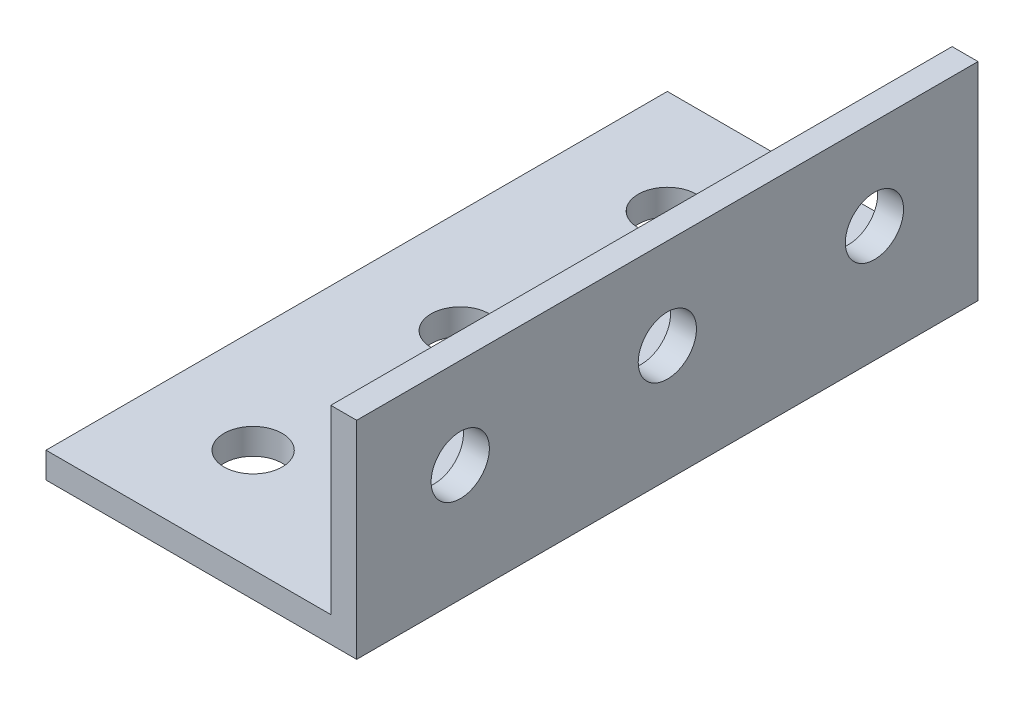
SolidWorks part; units mm, degrees
ref_plane "Front Plane" through (0, 0, 0) normal (0, 0, 1) x (1, 0, 0)
ref_plane "Top Plane" through (0, 0, 0) normal (0, 1, 0) x (1, 0, 0)
ref_plane "Right Plane" through (0, 0, 0) normal (1, 0, 0) x (0, 0, -1)
sketch "Sketch1" plane through (0, 0, 0) normal (0, 0, 1) x (1, 0, 0)
  line L0 (0, 0) -> (38.1, 0)
  line L1 (38.1, 0) -> (38.1, 25.4)
  line L2 (38.1, 25.4) -> (34.925, 25.4)
  line L3 (34.925, 25.4) -> (34.925, 3.175)
  line L4 (34.925, 3.175) -> (0, 3.175)
  line L5 (0, 3.175) -> (0, 0)
  dimension "D1" = 38.1
  dimension "D2" = 25.4
  dimension "D3" = 3.175
extrude "Boss-Extrude1" add sketch "Sketch1" along normal blind 76.2 contours L4 L5 L0 L1 L2 L3
sketch "Sketch6" plane through (0, 3.175, 0) normal (0, 1, 0) x (1, 0, 0)
  line L0 (12.7, -76.2) -> (12.7, 0) construction
  line L1 (34.925, -76.2) -> (0, -76.2) construction
  line L2 (34.925, 0) -> (0, 0) construction
  line L5 (34.925, -76.2) -> (34.925, 0) construction
  line L6 (12.7, -63.5) -> (12.7, -38.1) construction
  point P8 (12.7, -63.5)
  point P38 (12.7, -38.1)
  point P39 (12.7, -12.7)
  dimension "D1" = 22.225
  dimension "D2" = 12.7
  dimension "D4" = 25.4
  dimension "D3" = 3
hole_wizard "1/4 Clearance Hole1" positions "Sketch6" profile "Sketch7" hole size "1/4" standard "ANSI Inch" end condition up to next
sketch "Sketch7" plane through (12.7, 3.175, 12.7) normal (1, 0, 0) x (0, 0, 1)
  line L0 (0, 0) -> (0, 3.175)
  line L1 (0, 3.175) -> (3.5712, 3.175)
  line L2 (3.5712, 3.175) -> (3.5712, 0)
  line L5 (3.5712, 0) -> (0, 0)
  line L11 (0, -6.35) -> (0, 107.95) construction
  dimension "Thru Hole Dia." = 7.1425
  dimension "Thru Hole Depth" = 3.175
sketch "Sketch8" plane through (34.925, 0, 0) normal (-1, 0, 0) x (0, 0, 1)
  line L0 (0, 14.2875) -> (76.2, 14.2875) construction
  line L1 (0, 25.4) -> (0, 3.175) construction
  line L2 (76.2, 25.4) -> (76.2, 3.175) construction
  line L4 (12.7, 14.2875) -> (38.1, 14.2875) construction
  point P6 (12.7, 14.2875)
  point P26 (38.1, 14.2875)
  point P27 (63.5, 14.2875)
  point P28 (88.9, 14.2875)
  point P29 (114.3, 14.2875)
  point P30 (139.7, 14.2875)
  point P31 (165.1, 14.2875)
  point P32 (190.5, 14.2875)
  dimension "D1" = 12.7
  dimension "D3" = 25.4
  dimension "D2" = 8
hole_wizard "1/4 Clearance Hole2" positions "Sketch8" profile "Sketch9" hole size "1/4" standard "ANSI Inch" end condition up to next
sketch "Sketch9" plane through (34.925, 14.2875, 190.5) normal (0, 1, 0) x (0, 0, 1)
  line L0 (0, 0) -> (0, 3.175)
  line L1 (0, 3.175) -> (3.5712, 3.175)
  line L2 (3.5712, 3.175) -> (3.5712, 0)
  line L5 (3.5712, 0) -> (0, 0)
  line L11 (0, -6.35) -> (0, 107.95) construction
  dimension "Thru Hole Dia." = 7.1425
  dimension "Thru Hole Depth" = 3.175
